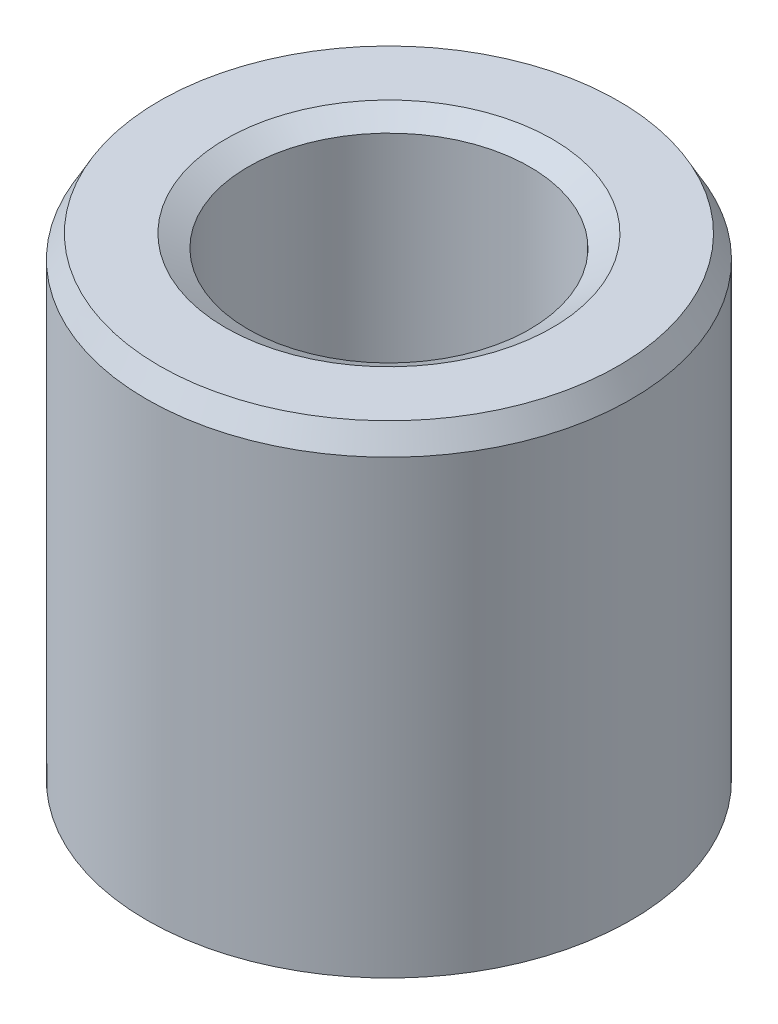
SolidWorks part; units mm, degrees
ref_plane "Front Plane" through (0, 0, 0) normal (0, 0, 1) x (1, 0, 0)
ref_plane "Top Plane" through (0, 0, 0) normal (0, 1, 0) x (1, 0, 0)
ref_plane "Right Plane" through (0, 0, 0) normal (1, 0, 0) x (0, 0, -1)
sketch "Sketch1" plane through (0, 0, 0) normal (0, 1, 0) x (1, 0, 0)
  circle A0 centre (0, 0) radius 30
  dimension "SLEEVE_OD" = 60
extrude "Boss-Extrude1" add sketch "Sketch1" along normal blind 60.238
sketch "Sketch2" plane through (0, 0, 0) normal (0, 1, 0) x (1, 0, 0)
  circle A0 centre (0, 0) radius 17.4355
  dimension "BORE_D" = 34.871
extrude "Cut-Extrude1" cut sketch "Sketch2" along normal through all
chamfer "Chamfer1" distance 2.801 angle 29.33 4 edges at (0, 60.238, 17.4355) (0, 0, 17.4355) (0, 0, 30) (0, 60.238, 30) first distance on face at (0, 60.238, 17.4355) first distance on face at (0, 0, 17.4355) first distance on face at (0, 60.238, 30)
